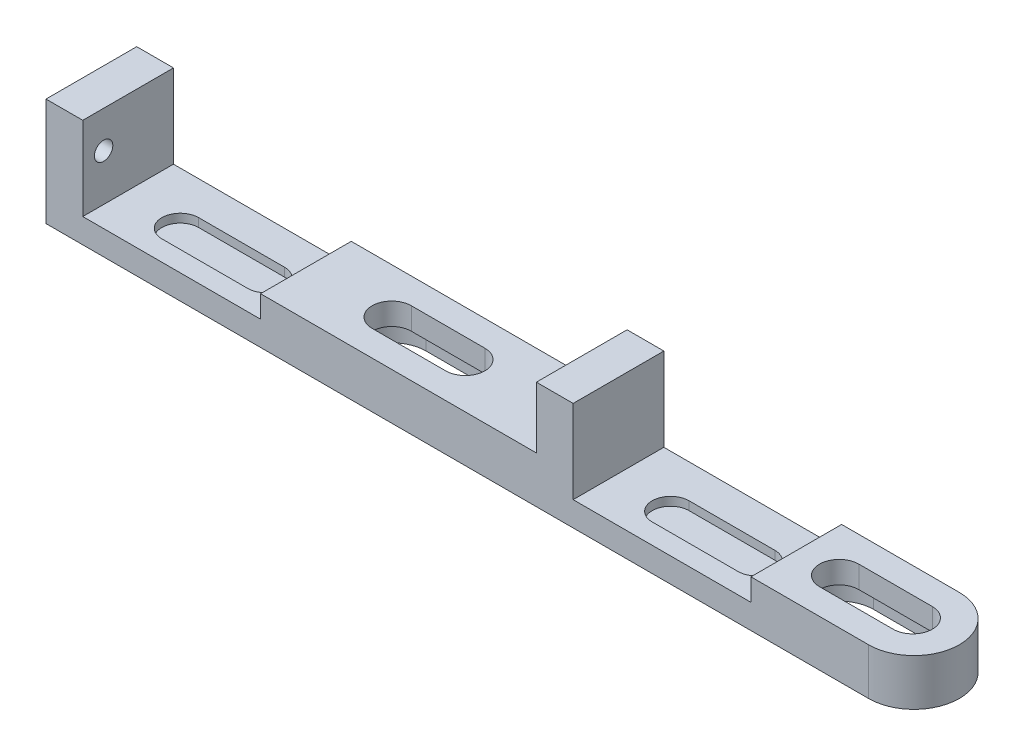
SolidWorks part; units mm, degrees
material "6061 Alloy"
ref_plane "Front Plane" through (0, 0, 0) normal (0, 0, 1) x (1, 0, 0)
ref_plane "Top Plane" through (0, 0, 0) normal (0, 1, 0) x (1, 0, 0)
ref_plane "Right Plane" through (0, 0, 0) normal (1, 0, 0) x (0, 0, -1)
sketch "Sketch1" plane through (0, 0, 0) normal (0, 0, 1) x (1, 0, 0)
  line L0 (0, 0) -> (0, 8.8)
  line L1 (0, 0) -> (70.8, 0)
  line L8 (70.8, 0) -> (70.8, 3.8)
  line L10 (0, 8.8) -> (3, 8.8)
  line L11 (3, 8.8) -> (3, 2)
  line L20 (40, 3.8) -> (40, 8.8)
  line L21 (40, 8.8) -> (43, 8.8)
  line L22 (43, 8.8) -> (43, 2)
  line L23 (40, 3.8) -> (17.5, 3.8)
  line L24 (17.5, 3.8) -> (17.5, 2)
  line L25 (17.5, 2) -> (3, 2)
  line L26 (70.8, 3.8) -> (57.5, 3.8)
  line L27 (57.5, 3.8) -> (57.5, 2)
  line L28 (57.5, 2) -> (43, 2)
  dimension "D1" = 3
  dimension "D2" = 2
  dimension "D3" = 8.8
  dimension "D4" = 3.8
  dimension "D5" = 14.5
  dimension "D6" = 3
  dimension "D7" = 40
  dimension "D8" = 14.5
  dimension "D10" = 70.8
extrude "Boss-Extrude1" add sketch "Sketch1" along normal blind 7.4
sketch "Sketch3" plane through (0, 3.8, 0) normal (0, 1, 0) x (1, 0, 0)
  line L0 (30.5, -3.7) -> (24.5, -3.7) construction
  line L1 (30.5, -5.3) -> (24.5, -5.3)
  line L2 (30.5, -2.1) -> (24.5, -2.1)
  line L3 (67, -3.7) -> (61, -3.7) construction
  line L4 (67, -5.3) -> (61, -5.3)
  line L5 (67, -2.1) -> (61, -2.1)
  line L6 (40, -7.4) -> (40, 0) construction
  arc A0 (30.5, -5.3) -> (30.5, -2.1) centre (30.5, -3.7) ccw
  arc A1 (24.5, -2.1) -> (24.5, -5.3) centre (24.5, -3.7) ccw
  arc A2 (67, -5.3) -> (67, -2.1) centre (67, -3.7) ccw
  arc A3 (61, -2.1) -> (61, -5.3) centre (61, -3.7) ccw
  point P2 (27.5, -3.7)
  point P7 (64, -3.7)
  point P21 (40, -3.7)
  dimension "D2" = 1.6
  dimension "D1" = 6
  dimension "D3" = 12.5
  dimension "D4" = 36.5
extrude "Cut-Extrude1" cut sketch "Sketch3" against normal blind 10
sketch "Sketch4" plane through (0, 0, 0) normal (0, -1, 0) x (1, 0, 0)
  line L0 (24.5, 5.3) -> (30.5, 5.3) construction
  line L1 (30.5, 2.1) -> (24.5, 2.1) construction
  line L2 (24.5, 5.3) -> (30.5, 5.3)
  line L3 (30.5, 2.1) -> (24.5, 2.1)
  line L4 (61, 5.3) -> (67, 5.3) construction
  line L5 (67, 2.1) -> (61, 2.1) construction
  line L6 (61, 5.3) -> (67, 5.3)
  line L7 (67, 2.1) -> (61, 2.1)
  line L8 (24.5, 6.5) -> (30.5, 6.5)
  line L9 (30.5, 0.9) -> (24.5, 0.9)
  line L10 (61, 6.5) -> (67, 6.5)
  line L11 (67, 0.9) -> (61, 0.9)
  arc A0 (30.5, 2.1) -> (30.5, 5.3) centre (30.5, 3.7) ccw construction
  arc A1 (24.5, 5.3) -> (24.5, 2.1) centre (24.5, 3.7) ccw construction
  arc A2 (30.5, 2.1) -> (30.5, 5.3) centre (30.5, 3.7) ccw
  arc A3 (24.5, 5.3) -> (24.5, 2.1) centre (24.5, 3.7) ccw
  arc A4 (61, 5.3) -> (61, 2.1) centre (61, 3.7) ccw construction
  arc A5 (67, 2.1) -> (67, 5.3) centre (67, 3.7) ccw construction
  arc A6 (61, 5.3) -> (61, 2.1) centre (61, 3.7) ccw
  arc A7 (67, 2.1) -> (67, 5.3) centre (67, 3.7) ccw
  arc A8 (30.5, 0.9) -> (30.5, 6.5) centre (30.5, 3.7) ccw
  arc A9 (24.5, 6.5) -> (24.5, 0.9) centre (24.5, 3.7) ccw
  arc A10 (67, 0.9) -> (67, 6.5) centre (67, 3.7) ccw
  arc A11 (61, 6.5) -> (61, 0.9) centre (61, 3.7) ccw
  dimension "D1" = 1.2
  dimension "D2" = 1.2
extrude "Cut-Extrude2" cut sketch "Sketch4" against normal blind 2
sketch "Sketch5" plane through (0, 0, 0) normal (-1, 0, 0) x (0, 0, 1)
  line L0 (7.4, 8.8) -> (0, 8.8) construction
  line L2 (7.4, 8.8) -> (7.4, 0) construction
  circle A0 centre (5.7, 5.8) radius 0.75
  dimension "D1" = 1.5
  dimension "D2" = 3
  dimension "D3" = 1.7
extrude "Cut-Extrude3" cut sketch "Sketch5" against normal up to next
sketch "Sketch6" plane through (0, 0, 0) normal (0, -1, 0) x (1, 0, 0)
  line L0 (70.8, 0) -> (70.8, 7.4)
  line L1 (70.8, 7.4) -> (70.8, 0) construction
  line L2 (70.8, 7.4) -> (67.1, 7.4)
  line L3 (0, 7.4) -> (70.8, 7.4) construction
  line L4 (0, 0) -> (70.8, 0) construction
  line L5 (67.1, 0) -> (70.8, 0)
  arc A0 (67.1, 7.4) -> (67.1, 0) centre (67.1, 3.7) cw
extrude "Cut-Extrude4" cut sketch "Sketch6" against normal blind 10 contours A0 | A0 L0 region at (69.9735, 0, 0.8265) region at (69.9735, 0, 6.5735)
sketch "Sketch7" [suppressed] plane through (0, 2, 0) normal (0, 1, 0) x (1, 0, 0)
  line L0 (54.8, -3.15) -> (47.8, -3.15) construction
  line L1 (54.8, -4.65) -> (47.8, -4.65)
  line L2 (54.8, -1.65) -> (47.8, -1.65)
  line L3 (14.8, -3.15) -> (7.8, -3.15) construction
  line L4 (14.8, -4.65) -> (7.8, -4.65)
  line L5 (14.8, -1.65) -> (7.8, -1.65)
  line L6 (57.5, 0) -> (43, 0) construction
  line L7 (57.5, -7.4) -> (57.5, 0) construction
  line L8 (17.5, -7.4) -> (17.5, 0) construction
  arc A0 (54.8, -4.65) -> (54.8, -1.65) centre (54.8, -3.15) ccw
  arc A1 (47.8, -1.65) -> (47.8, -4.65) centre (47.8, -3.15) ccw
  arc A2 (14.8, -4.65) -> (14.8, -1.65) centre (14.8, -3.15) ccw
  arc A3 (7.8, -1.65) -> (7.8, -4.65) centre (7.8, -3.15) ccw
  point P2 (51.3, -3.15)
  point P7 (11.3, -3.15)
  point P16 (50.25, 0)
  dimension "D2" = 1.5
  dimension "D4" = 2.7
  dimension "D5" = 2.7
  dimension "D1" = 3.15
  dimension "D3" = 7
extrude "Cut-Extrude5" [suppressed] cut sketch "Sketch7" against normal blind 0.7
sketch "Sketch8" plane through (0, 2, 0) normal (0, 1, 0) x (1, 0, 0)
  line L0 (7.8, -4.25) -> (14.8, -4.25) construction
  line L1 (7.8, -2.75) -> (14.8, -2.75)
  line L2 (7.8, -5.75) -> (14.8, -5.75)
  line L3 (47.8, -4.25) -> (54.8, -4.25) construction
  line L4 (47.8, -2.75) -> (54.8, -2.75)
  line L5 (47.8, -5.75) -> (54.8, -5.75)
  line L6 (17.5, -7.4) -> (17.5, 0) construction
  line L7 (17.5, -7.4) -> (3, -7.4) construction
  line L8 (57.5, -7.4) -> (57.5, 0) construction
  arc A0 (7.8, -2.75) -> (7.8, -5.75) centre (7.8, -4.25) ccw
  arc A1 (14.8, -5.75) -> (14.8, -2.75) centre (14.8, -4.25) ccw
  arc A2 (47.8, -2.75) -> (47.8, -5.75) centre (47.8, -4.25) ccw
  arc A3 (54.8, -5.75) -> (54.8, -2.75) centre (54.8, -4.25) ccw
  point P2 (11.3, -4.25)
  point P7 (51.3, -4.25)
  dimension "D2" = 2.7
  dimension "D3" = 1.5
  dimension "D5" = 2.7
  dimension "D1" = 7
  dimension "D4" = 3.15
extrude "Cut-Extrude6" cut sketch "Sketch8" against normal blind 0.7
